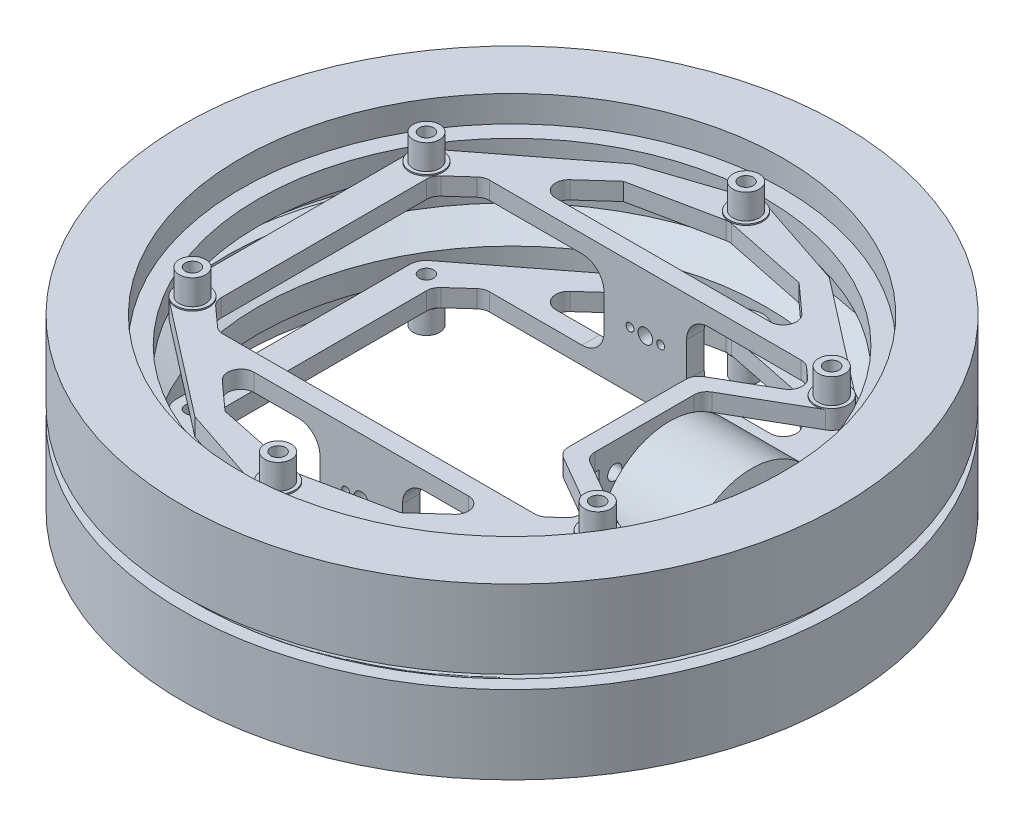
SolidWorks part; units mm, degrees
material "ABS"
ref_plane "Front Plane" through (0, 0, 0) normal (0, 0, 1) x (1, 0, 0)
ref_plane "Top Plane" through (0, 0, 0) normal (0, 1, 0) x (1, 0, 0)
ref_plane "Right Plane" through (0, 0, 0) normal (1, 0, 0) x (0, 0, -1)
other "Center of Mass"
ref_axis "Axis1" through (0, -45.4923, 0) along (0, 1, 0)
sketch "Sketch3" plane through (0, 0, 0) normal (0, 0, 1) x (1, 0, 0)
  line L0 (65, 1.5) -> (75, 1.5)
  line L1 (75, 1.5) -> (75, 19.3)
  line L2 (75, 19.3) -> (61.7495, 19.3)
  line L3 (0, 0) -> (85.6752, 0) construction
  line L4 (52.3451, 13.8) -> (57.3812, 3)
  line L5 (65, 1.5) -> (65, 4.5601)
  line L14 (35.8451, 16.3) -> (35.8451, 13.8)
  line L15 (35.8451, 13.8) -> (52.3451, 13.8)
  line L17 (54.4894, 16.3) -> (35.8451, 16.3)
  line L22 (0, -45.4923) -> (0, 86.3395) construction
  line L23 (57.3812, 3) -> (64.5, 3)
  line L24 (64.5, 3) -> (64.5, 7)
  line L25 (64.5, 7) -> (57.2495, 10.3809)
  line L26 (57.2495, 10.3809) -> (54.4894, 16.3)
  line L27 (65, 4.5601) -> (57.7495, 7.941)
  line L28 (57.7495, 7.941) -> (57.7495, 13.3)
  line L29 (57.7495, 13.3) -> (61.7495, 13.3)
  line L30 (61.7495, 13.3) -> (61.7495, 19.3)
  line L31 (53.2495, 19.3) -> (53.2495, 13.3) construction
  line L32 (44.7495, 19.3) -> (61.7495, 19.3) construction
  line L33 (44.7495, 19.3) -> (44.7495, 13.3) construction
  line L34 (44.7495, 13.3) -> (61.7495, 13.3) construction
  line L35 (61.7495, 19.3) -> (61.7495, 13.3) construction
  line L36 (50.2495, 19.3) -> (50.2495, 13.3) construction
  line L37 (56.2495, 19.3) -> (56.2495, 13.3) construction
  line L38 (75, -1.5) -> (75, -19.3)
  line L39 (65, -1.5) -> (75, -1.5)
  line L40 (65, -1.5) -> (65, -4.5601)
  line L41 (65, -4.5601) -> (57.7495, -7.941)
  line L42 (57.7495, -7.941) -> (57.7495, -13.3)
  line L43 (57.7495, -13.3) -> (61.7495, -13.3)
  line L44 (61.7495, -13.3) -> (61.7495, -19.3)
  line L45 (75, -19.3) -> (61.7495, -19.3)
  circle A0 centre (70, 0) radius 2.5
  point P34 (70, 1.5)
  dimension "D6" = 3
  dimension "D7" = 5
  dimension "D3" = 0.5
  dimension "D4" = 115
  dimension "D5" = 3
  dimension "D8" = 17
  dimension "D9" = 4
  dimension "D10" = 2.5
  dimension "D11" = 65
  dimension "D12" = 25
  dimension "D13" = 6
  dimension "D16" = 10
  dimension "D17" = 8
  dimension "D18" = 27.6
  dimension "D19" = 16.5
  dimension "D20" = 3
  dimension "D21" = 7
  dimension "D22" = 3
  dimension "D23" = 0.5
  dimension "D24" = 75
  dimension "D25" = 2
  dimension "D14" = 3
  dimension "D15" = 3
revolve "Revolve1" add sketch "Sketch3" angle 360 about axis through (0, -45.4923, 0) along (0, 1, 0) region at (68.168, 11.0369, 0) region at (67.7412, -10.8207, 0) region at (61.1248, 7.4705, 0)
revolve "Revolve2" add sketch "Sketch3<3>" angle 360 about L3 region at (61.1248, 7.4705, 0) region at (64.1841, 3.8966, 0)
sketch "Sketch3<3>" plane through (0, 0, 0) normal (0, 0, 1) x (1, 0, 0) same geometry as "Sketch3"
sketch "Sketch4" plane through (0, 0, 0) normal (0, 1, 0) x (1, 0, 0)
  line L0 (0, 0) -> (0, 53.2495) construction
  line L1 (0, 0) -> (46.1155, 26.6248) construction
  line L2 (0, 0) -> (46.1155, -26.6248) construction
  line L3 (0, 0) -> (0, -53.2495) construction
  line L4 (0, 0) -> (-46.1155, -26.6248) construction
  line L5 (0, 0) -> (-46.1155, 26.6248) construction
  line L6 (-1.2011, 56.8547) -> (-22.3876, 49.7965)
  line L7 (-48.4414, 29.6297) -> (-22.3876, 49.7965)
  line L8 (-49.9155, 26.6248) -> (-49.9155, -26.6248)
  line L9 (48.4414, 29.6297) -> (22.3876, 49.7965)
  line L10 (1.2011, 56.8547) -> (22.3876, 49.7965)
  line L11 (0, 0) -> (130.3481, 0) construction
  line L12 (48.0155, 23.3339) -> (30.1301, 13.0077)
  line L13 (30.1301, 13.0077) -> (30.1301, -13.0077)
  line L14 (48.0155, -23.3339) -> (30.1301, -13.0077)
  line L15 (35.8451, 13.8) -> (35.8451, -13.8) construction
  line L16 (48.4414, -29.6297) -> (22.3876, -49.7965)
  line L17 (-20, 45.3218) -> (20, 45.3218) construction
  line L18 (-20, 45.3218) -> (-20, 35.3218) construction
  line L19 (-20, 35.3218) -> (20, 35.3218) construction
  line L20 (20, 45.3218) -> (20, 35.3218) construction
  line L21 (1.2011, -56.8547) -> (22.3876, -49.7965)
  line L22 (-1.2011, -56.8547) -> (-22.3876, -49.7965)
  line L23 (-48.4414, -29.6297) -> (-22.3876, -49.7965)
  line L24 (-20, 45.3218) -> (-42.8246, 24.7248)
  line L25 (-20, 45.3218) -> (0, 49.4495)
  line L26 (0, 49.4495) -> (20, 45.3218)
  line L27 (20, 45.3218) -> (42.8246, 24.7248)
  line L28 (-32.1896, 34.3218) -> (32.1896, 34.3218)
  line L29 (-36.6222, 30.3218) -> (36.6222, 30.3218)
  line L30 (-42.8246, 24.7248) -> (-42.8246, -24.7248)
  line L31 (26.1301, -15.0862) -> (26.1301, 15.0862)
  line L32 (26.1301, 15.0862) -> (42.8246, 24.7248)
  line L33 (-32.1896, -34.3218) -> (32.1896, -34.3218)
  line L34 (-36.6222, -30.3218) -> (36.6222, -30.3218)
  line L35 (-20, -45.3218) -> (-42.8246, -24.7248)
  line L36 (0, -49.4495) -> (20, -45.3218)
  line L37 (-20, -45.3218) -> (0, -49.4495)
  line L38 (20, -45.3218) -> (42.8246, -24.7248)
  line L39 (26.1301, -15.0862) -> (42.8246, -24.7248)
  circle A1 centre (0, 53.2495) radius 3
  circle A3 centre (0, 53.2495) radius 3.8
  circle A4 centre (0, 53.2495) radius 1.65
  circle A5 centre (46.1155, 26.6248) radius 1.65
  circle A6 centre (46.1155, 26.6248) radius 3
  circle A7 centre (46.1155, 26.6248) radius 3.8
  circle A8 centre (46.1155, -26.6248) radius 1.65
  circle A9 centre (46.1155, -26.6248) radius 3
  circle A10 centre (46.1155, -26.6248) radius 3.8
  circle A11 centre (0, -53.2495) radius 1.65
  circle A12 centre (0, -53.2495) radius 3
  circle A13 centre (0, -53.2495) radius 3.8
  circle A14 centre (-46.1155, -26.6248) radius 1.65
  circle A15 centre (-46.1155, -26.6248) radius 3
  circle A16 centre (-46.1155, -26.6248) radius 3.8
  circle A17 centre (-46.1155, 26.6248) radius 1.65
  circle A18 centre (-46.1155, 26.6248) radius 3
  circle A19 centre (-46.1155, 26.6248) radius 3.8
  circle A20 centre (0, 53.2495) radius 8.5
  circle A21 centre (0, 0) radius 61.7495 construction
  point P32 (0, 0)
  point P44 (0, 45.3218)
  point P48 (30.1301, 0)
  point P63 (-49.9155, 0)
  point P78 (-42.8246, 0)
  point P83 (26.1301, 0)
  dimension "D1" = 6
  dimension "D2" = 17
  dimension "D4" = 0.8
  dimension "D5" = 3.3
  dimension "D13" = 1
  dimension "D7" = 5.715
  dimension "D8" = 10
  dimension "D9" = 40
  dimension "D10" = 5
  dimension "D11" = 5
  dimension "D12" = 4.1278
  dimension "D14" = 4
  dimension "D15" = 4
  dimension "D6" = 6
extrude "Boss-Extrude1" add sketch "Sketch4" along normal blind 4 from offset 9 separate body contours A19 L24 L25 A3 L6 L7 | A7 L9 L10 A3 L26 L27 | A3 A1 | A1 A4 | A7 A6 | A6 A5 | A10 L14 L13 L12 A7 L32 L31 L39 | A10 A9 | A9 A8 | A13 L21 L16 A10 L38 L36 | A12 A11 | A16 L23 L22 A13 L37 L35 | A13 A12 | A16 A15 | A15 A14 | A19 L8 A16 L30 | A19 A18 | A18 A17 | L24 L29 L27 L28 | L33 L38 L34 L35 | L26 A20 L10 A3 | L6 A20 L25 A3 region at (-5.4103, 0, -51.8523) region at (0, 0, -56.9421) region at (-27.4512, 0, -41.1917) region at (5.4103, 0, -51.8523) region at (27.4512, 0, -41.1917) region at (-44.4893, 0, -29.9399) region at (-46.3899, 0, 0) region at (49.4306, 0, -28.2509) region at (0, 0, -32.2788) region at (-47.0711, 0, 23.0581) region at (44.992, 0, -22.4319) region at (-24.7667, 0, 42.4901) region at (0, 0, 32.2788) region at (24.7667, 0, 42.4901) region at (-3.6449, 0, 52.6584) region at (45.1598, 0, 23.0581) region at (-2.9151, 0, -53.2495) region at (43.2003, 0, -26.6248) region at (43.2003, 0, 26.6248) region at (-2.9151, 0, 53.2495) region at (-49.0306, 0, 26.6248) region at (-49.0306, 0, -26.6248)
extrude "Boss-Extrude5" add sketch "Sketch4<3>" along normal up to surface (13.3 mm away) from surface contours A3 A1 | A1 A4 | A6 A5 | A7 A6 | A9 A8 | A10 A9 | A13 A12 | A12 A11 | A16 A15 | A15 A14 | A19 A18 | A18 A17 region at (0, 0, -56.9421) region at (-44.4893, 0, -29.9399) region at (49.4306, 0, -28.2509) region at (-47.0711, 0, 23.0581) region at (-3.6449, 0, 52.6584) region at (45.1598, 0, 23.0581) region at (-2.9151, 0, -53.2495) region at (43.2003, 0, -26.6248) region at (43.2003, 0, 26.6248) region at (-2.9151, 0, 53.2495) region at (-49.0306, 0, 26.6248) region at (-49.0306, 0, -26.6248) up to face at (0, 13.3, -61.7495) starting at face at (3.2844, 9, 0)
sketch "Sketch4<3>" plane through (0, 0, 0) normal (0, 1, 0) x (1, 0, 0) same geometry as "Sketch4"
extrude "Boss-Extrude6" add sketch "Sketch4<4>" along normal blind 6 from surface contours A18 A17 | A15 A14 | A12 A11 | A9 A8 | A6 A5 | A1 A4 region at (-2.9151, 0, -53.2495) region at (43.2003, 0, -26.6248) region at (43.2003, 0, 26.6248) region at (-2.9151, 0, 53.2495) region at (-49.0306, 0, 26.6248) region at (-49.0306, 0, -26.6248) starting at face at (0, 13, 40.2774)
sketch "Sketch4<4>" plane through (0, 0, 0) normal (0, 1, 0) x (1, 0, 0) same geometry as "Sketch4"
fillet "Fillet2" radius 3 18 edges at (30.1301, 11, -13.0077) (30.1301, 11, 13.0077) (32.1896, 11, -34.3218) (-32.1896, 11, -34.3218) (0, 11, -49.4495) (32.1896, 11, 34.3218) (-32.1896, 11, 34.3218) (0, 11, 49.4495) (-36.6222, 11, -30.3218) (36.6222, 11, -30.3218) (42.8246, 11, -24.7248) (26.1301, 11, -15.0862) (26.1301, 11, 15.0862) (42.8246, 11, 24.7248) (36.6222, 11, 30.3218) (-42.8246, 11, 24.7248) (-42.8246, 11, -24.7248) (-36.6222, 11, 30.3218)
mirror "Mirror2" about plane through (0, 0, 0) normal (0, 1, 0) of bodies 113 105
sketch "Sketch7" plane through (26.1301, 0, 0) normal (-1, 0, 0) x (0, 0, 1)
  line L0 (13.3542, -9) -> (-13.3542, -9) construction
  line L1 (-10.3852, -9) -> (10.3852, -9)
  line L2 (-10.3852, -9) -> (-10.3852, 9)
  line L3 (-10.3852, 9) -> (10.3852, 9)
  line L4 (10.3852, -9) -> (10.3852, 9)
  line L5 (13.3542, 9) -> (-13.3542, 9) construction
  line L6 (-6.7352, -6.7352) -> (6.7352, 6.7352) construction
  line L7 (-5.5508, 5.5508) -> (5.5508, -5.5508) construction
  circle A0 centre (6.7352, 6.7352) radius 1.65
  circle A1 centre (-5.5508, 5.5508) radius 1.65
  circle A2 centre (-6.7352, -6.7352) radius 1.65
  circle A3 centre (5.5508, -5.5508) radius 1.65
  point P9 (0, -9)
  dimension "D3" = 3.3
  dimension "D6" = 2
  dimension "D1" = 90
  dimension "D2" = 45
  dimension "D4" = 19.05
  dimension "D5" = 15.7
extrude "Boss-Extrude7" add sketch "Sketch7" against normal up to surface (4 mm away) up to face at (30.1301, 11, 0)
sketch "Sketch8" plane through (0, 0, -30.3218) normal (0, 0, 1) x (1, 0, 0)
  line L0 (1.2011, 9) -> (22.3876, 9) construction
  line L1 (-9.4, -9) -> (9.4, -9)
  line L2 (-9.4, -9) -> (-9.4, 9)
  line L3 (-9.4, 9) -> (9.4, 9)
  line L4 (9.4, -9) -> (9.4, 9)
  line L5 (-9.4, -9) -> (9.4, 9) construction
  line L6 (-9.4, 9) -> (9.4, -9) construction
  line L7 (-3.5, 0) -> (3.5, 0) construction
  circle A0 centre (0, 0) radius 1.65
  circle A1 centre (-3.5, 0) radius 0.9
  circle A2 centre (3.5, 0) radius 0.9
  point P0 (0, 0)
  dimension "D1" = 1.8
  dimension "D2" = 7
  dimension "D3" = 3.3
  dimension "D4" = 5
extrude "Boss-Extrude8" add sketch "Sketch8" against normal blind 4
mirror "Mirror4" about plane through (0, 0, 0) normal (0, 0, 1) of "Boss-Extrude8"
fillet "Fillet1" radius 5 8 edges at (-9.4, -9, 32.3218) (-9.4, 9, 32.3218) (-9.4, 9, -32.3218) (-9.4, -9, -32.3218) (9.4, -9, 32.3218) (9.4, 9, 32.3218) (9.4, 9, -32.3218) (9.4, -9, -32.3218)
